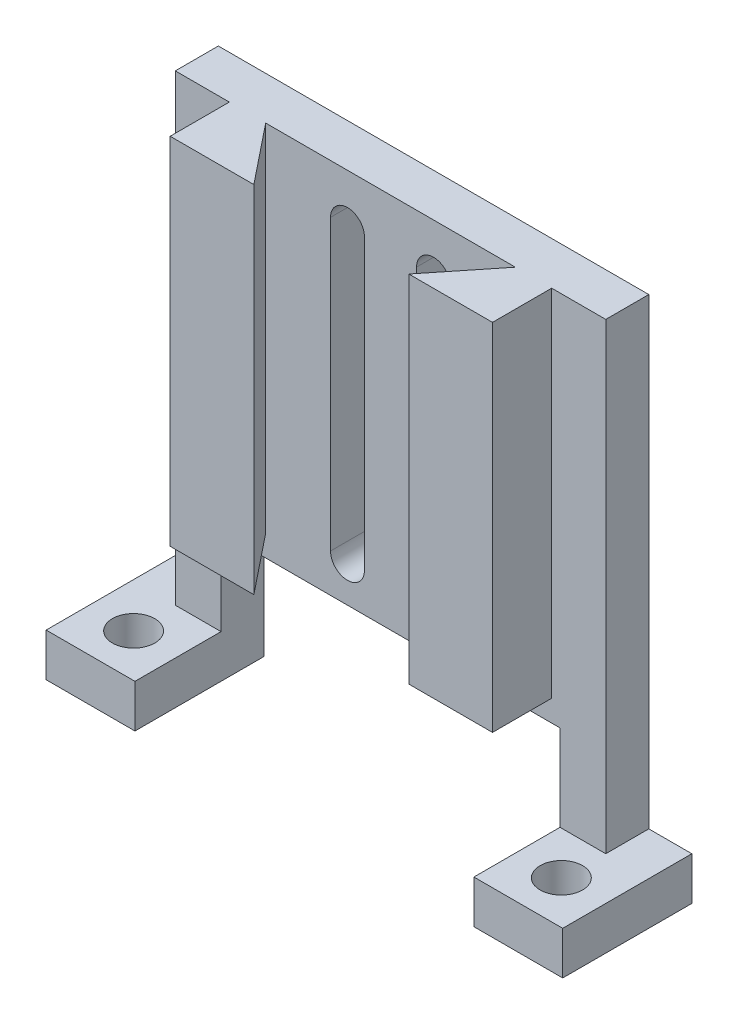
SolidWorks part; units mm, degrees
ref_plane "Front Plane" through (0, 0, 0) normal (0, 0, 1) x (1, 0, 0)
ref_plane "Top Plane" through (0, 0, 0) normal (0, 1, 0) x (1, 0, 0)
ref_plane "Right Plane" through (0, 0, 0) normal (1, 0, 0) x (0, 0, -1)
sketch "Sketch1" plane through (0, 0, 0) normal (0, 0, 1) x (1, 0, 0)
  line L0 (20.32, 54.61) -> (20.32, 0) construction
  line L1 (0, 0) -> (50.8, 0)
  line L2 (0, 0) -> (0, 54.61)
  line L3 (0, 54.61) -> (50.8, 54.61)
  line L4 (50.8, 0) -> (50.8, 54.61)
  line L5 (25.4, 54.61) -> (25.4, 0) construction
  line L6 (0, 27.305) -> (50.8, 27.305) construction
  line L7 (30.48, 54.61) -> (30.48, 0) construction
  line L8 (0, 50.8) -> (50.8, 50.8) construction
  line L9 (0, 3.81) -> (50.8, 3.81) construction
  line L10 (20.32, 5.81) -> (20.32, 48.8) construction
  line L11 (18.32, 5.81) -> (18.32, 48.8) construction
  line L12 (22.32, 5.81) -> (22.32, 48.8) construction
  line L13 (30.48, 5.81) -> (30.48, 48.8) construction
  line L14 (32.48, 5.81) -> (32.48, 48.8) construction
  line L15 (28.48, 5.81) -> (28.48, 48.8) construction
  arc A0 (18.32, 5.81) -> (22.32, 5.81) centre (20.32, 5.81) ccw construction
  arc A1 (22.32, 48.8) -> (18.32, 48.8) centre (20.32, 48.8) ccw construction
  arc A2 (32.48, 5.81) -> (28.48, 5.81) centre (30.48, 5.81) cw construction
  arc A3 (28.48, 48.8) -> (32.48, 48.8) centre (30.48, 48.8) cw construction
  point P14 (20.32, 27.305)
  point P19 (20.32, 50.8)
  point P20 (20.32, 3.81)
  point P23 (30.48, 27.305)
  point P272 (25.4, 27.305)
  dimension "D5" = 4
  dimension "D1" = 50.8
  dimension "D2" = 54.61
  dimension "D3" = 5.08
  dimension "D4" = 3.81
extrude "Boss-Extrude1" add sketch "Sketch1" along normal blind 5.08
sketch "Sketch2" plane through (0, 0, 0) normal (0, -1, 0) x (1, 0, 0)
  line L0 (25.4, 5.08) -> (25.4, 0) construction
  line L1 (0, 5.08) -> (50.8, 5.08) construction
  line L2 (0, 0) -> (50.8, 0) construction
  line L3 (10.922, 5.08) -> (39.878, 5.08) construction
  line L4 (25.4, 5.08) -> (25.4, 12.065) construction
  line L5 (16.51, 12.065) -> (34.29, 12.065) construction
  line L6 (16.51, 12.065) -> (10.922, 5.08) construction
  line L7 (34.29, 12.065) -> (39.878, 5.08) construction
  line L8 (10.668, 5.08) -> (6.3806, 5.08)
  line L9 (6.3806, 5.08) -> (6.3806, 12.065)
  line L10 (6.3806, 12.065) -> (16.256, 12.065)
  line L11 (16.256, 12.065) -> (10.668, 5.08)
  line L12 (34.544, 12.065) -> (40.132, 5.08)
  line L13 (44.4194, 12.065) -> (34.544, 12.065)
  line L14 (44.4194, 5.08) -> (44.4194, 12.065)
  line L15 (40.132, 5.08) -> (44.4194, 5.08)
  point P9 (25.4, 5.08)
  point P13 (25.4, 12.065)
  dimension "D1" = 28.956
  dimension "D2" = 6.985
  dimension "D3" = 17.78
  dimension "D4" = 9.8754
  dimension "D5" = 0.254
extrude "Boss-Extrude2" add sketch "Sketch2" against normal up to vertex (54.61 mm away) up to point (0, 54.61, 5.08)
sketch "Sketch3" plane through (0, 0, 5.08) normal (0, 0, 1) x (1, 0, 0)
  line L0 (0, 12.7) -> (50.8, 12.7) construction
  line L4 (25.4, 54.61) -> (25.4, 0) construction
  line L5 (0, 0) -> (0, 54.61) construction
  line L8 (50.8, 0) -> (50.8, 54.61) construction
  line L9 (0, 0) -> (50.8, 0) construction
  line L10 (20.32, 48.8) -> (20.32, 14.7) construction
  line L11 (22.32, 48.8) -> (22.32, 14.7)
  line L12 (18.32, 48.8) -> (18.32, 14.7)
  line L14 (30.48, 48.8) -> (30.48, 14.7) construction
  line L15 (28.48, 48.8) -> (28.48, 14.7)
  line L16 (32.48, 48.8) -> (32.48, 14.7)
  arc A5 (22.32, 48.8) -> (18.32, 48.8) centre (20.32, 48.8) ccw
  arc A6 (18.32, 14.7) -> (22.32, 14.7) centre (20.32, 14.7) ccw
  arc A7 (22.32, 48.8) -> (18.32, 48.8) centre (20.32, 48.8) ccw construction
  arc A8 (28.48, 48.8) -> (32.48, 48.8) centre (30.48, 48.8) cw
  arc A9 (32.48, 14.7) -> (28.48, 14.7) centre (30.48, 14.7) cw
  point P12 (20.32, 31.75)
  point P26 (20.32, 12.7)
  point P27 (30.48, 31.75)
  dimension "D1" = 12.7
extrude "Cut-Extrude1" cut sketch "Sketch3" against normal up to vertex (5.08 mm away) and the other way through all up to point (0, 54.61, 0)
sketch "Sketch4" plane through (0, 0, 0) normal (0, -1, 0) x (1, 0, 0)
  line L1 (0, 0) -> (50.8, 0)
  line L2 (0, 0) -> (0, 15.24)
  line L3 (0, 15.24) -> (50.8, 15.24)
  line L4 (50.8, 0) -> (50.8, 15.24)
  line L5 (25.4, 15.24) -> (25.4, 0) construction
  line L6 (0, 7.62) -> (50.8, 7.62) construction
  line L7 (50.8, 5.08) -> (50.8, 0) construction
  point P392 (25.4, 7.62)
  dimension "D1" = 15.24
extrude "Boss-Extrude3" add sketch "Sketch4" along normal blind 5.08
sketch "Sketch5" plane through (6.3806, 0, 0) normal (-1, 0, 0) x (0, 0, 1)
  line L0 (12.065, 54.61) -> (12.065, 0) construction
  line L1 (5.08, 0) -> (12.065, 0)
  line L2 (5.08, 0) -> (5.08, 12.7)
  line L3 (5.08, 12.7) -> (12.065, 12.7)
  line L4 (12.065, 0) -> (12.065, 12.7)
  line L5 (8.5725, 12.7) -> (8.5725, 0) construction
  line L6 (5.08, 6.35) -> (12.065, 6.35) construction
  point P212 (8.5725, 6.35)
  dimension "D1" = 12.7
extrude "Cut-Extrude2" cut sketch "Sketch5" against normal up to surface (38.0389 mm away) up to face at (44.4194, 27.305, 8.5725)
sketch "Sketch6" plane through (0, 0, 15.24) normal (0, 0, 1) x (1, 0, 0)
  line L0 (50.8, -5.08) -> (0, -5.08) construction
  line L1 (5.4, -5.08) -> (45.4, -5.08)
  line L2 (5.4, -5.08) -> (5.4, 10.16)
  line L3 (5.4, 10.16) -> (45.4, 10.16)
  line L4 (45.4, -5.08) -> (45.4, 10.16)
  line L5 (25.4, 10.16) -> (25.4, -5.08) construction
  line L6 (5.4, 2.54) -> (45.4, 2.54) construction
  line L7 (25.4, 54.61) -> (25.4, 0) construction
  point P460 (25.4, 2.54)
  dimension "D1" = 40
  dimension "D2" = 15.24
extrude "Cut-Extrude3" cut sketch "Sketch6" against normal up to surface (15.24 mm away) and the other way through all up to face at (20.32, 31.75, 0)
sketch "Sketch8" plane through (0, 0, 0) normal (-1, 0, 0) x (0, 0, 1)
  line L1 (15.24, -5.08) -> (0, -5.08)
  line L2 (15.24, -5.08) -> (15.24, 0)
  line L3 (15.24, 0) -> (0, 0)
  line L4 (0, -5.08) -> (0, 0)
  line L5 (7.62, 0) -> (7.62, -5.08) construction
  line L6 (15.24, -2.54) -> (0, -2.54) construction
  point P172 (7.62, -2.54)
extrude "Boss-Extrude4" add sketch "Sketch8" along normal blind 5.08
ref_axis "Axis1" through (25.4, 54.61, 5.08) along (0, -1, 0)
ref_plane "Plane1" through (25.4, 0, 0) normal (-1, 0, 0) x (0, 0, 1)
mirror "Mirror1" about plane through (25.4, 0, 0) normal (-1, 0, 0) of "Boss-Extrude4"
sketch "Sketch9" plane through (0, 0, 0) normal (0, 1, 0) x (1, 0, 0)
  line L0 (25.4, 0) -> (25.4, -5.08) construction
  line L1 (5.4, -5.08) -> (-5.08, -5.08) construction
  line L2 (5.4, -5.08) -> (5.4, -15.24) construction
  line L3 (5.4, -15.24) -> (-5.08, -15.24) construction
  line L4 (-5.08, -5.08) -> (-5.08, -15.24) construction
  line L5 (0.16, -15.24) -> (0.16, -5.08) construction
  line L6 (5.4, -10.16) -> (-5.08, -10.16) construction
  line L7 (50.8, 0) -> (0, 0) construction
  line L8 (40.132, -5.08) -> (10.668, -5.08) construction
  circle A0 centre (0.16, -10.16) radius 2.5
  circle A1 centre (50.64, -10.16) radius 2.5
  point P316 (0.16, -10.16)
  dimension "D1" = 5
extrude "Cut-Extrude4" cut sketch "Sketch9" against normal blind 5.08
equation "\"D1@Sketch5\"=\"D1@Sketch3\""
